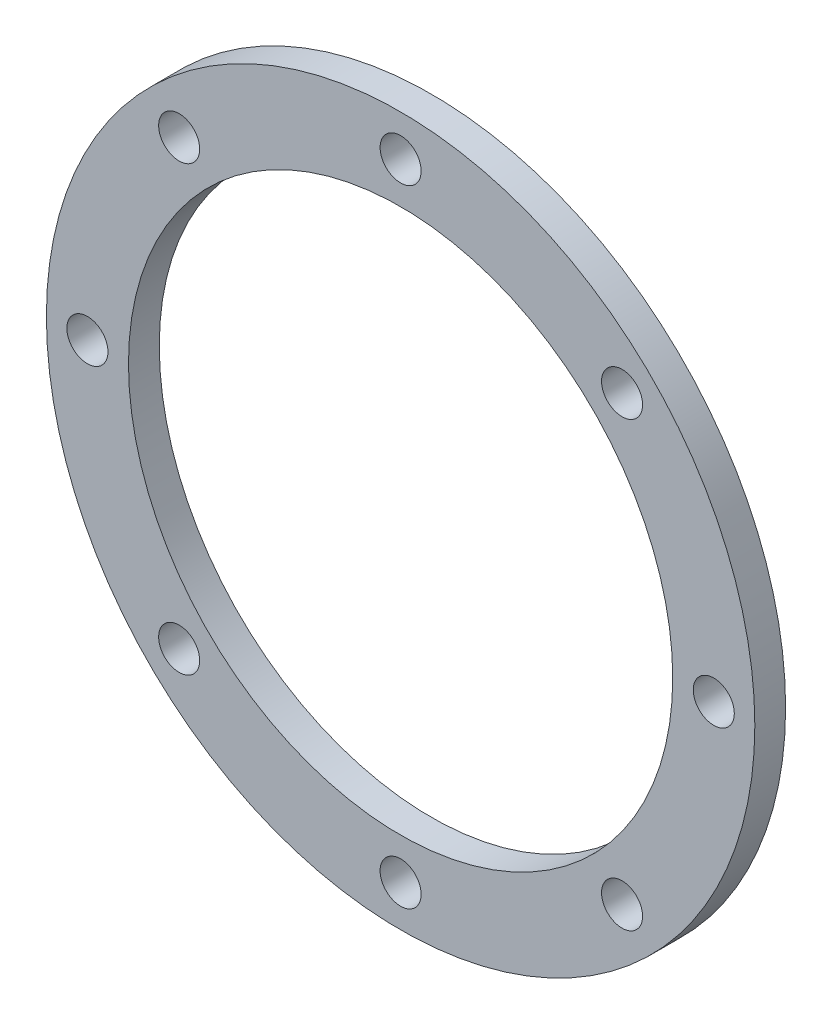
SolidWorks part; units mm, degrees
ref_plane "Front Plane" through (0, 0, 0) normal (0, 0, 1) x (1, 0, 0)
ref_plane "Top Plane" through (0, 0, 0) normal (0, 1, 0) x (1, 0, 0)
ref_plane "Right Plane" through (0, 0, 0) normal (1, 0, 0) x (0, 0, -1)
sketch "Sketch1" plane through (0, 0, 0) normal (0, 0, 1) x (1, 0, 0)
  circle A0 centre (0, 0) radius 84.201
  circle A1 centre (0, 0) radius 109.601
  dimension "D1" = 168.402
  dimension "D2" = 219.202
extrude "Extrude1" add sketch "Sketch1" along normal blind 9.525
hole_wizard "1/2 (0.5) Diameter Hole3" positions "3DSketch1" profile "Sketch2" hole size "1/2" standard "Ansi Inch"
sketch3d "3DSketch1"
  line L10 (0, 109.601, 9.525) -> (0, 0, 9.525) construction
  circle A2 centre (0, 0, 9.525) radius 109.601 construction
  circle A3 centre (0, 0, 9.525) radius 109.601 construction
  point P5 (0, 96.901, 9.525)
  point P24 (0, 0, 119.126)
  point P26 (0, 0, 119.126)
  dimension "D1" = 12.7
sketch "Sketch2" plane through (0, 96.901, 9.525) normal (1, 0, 0) x (0, -1, 0)
  line L0 (0, 0) -> (0, 29.2155)
  line L1 (0, 29.2155) -> (6.35, 25.4)
  line L2 (6.35, 25.4) -> (6.35, 0)
  line L5 (6.35, 0) -> (0, 0)
  line L10 (0, 29.2155) -> (-6.35, 25.4) construction
  line L11 (0, -6.35) -> (0, 107.95) construction
  dimension "Hole Dia." = 12.7
  dimension "Hole Depth" = 25.4
  dimension "Drill Angle" = 118
pattern_circular "CirPattern1" count 8 over 360 about axis through (0, 0, 9.525) along (0, 0, -1) of "1/2 (0.5) Diameter Hole3"
